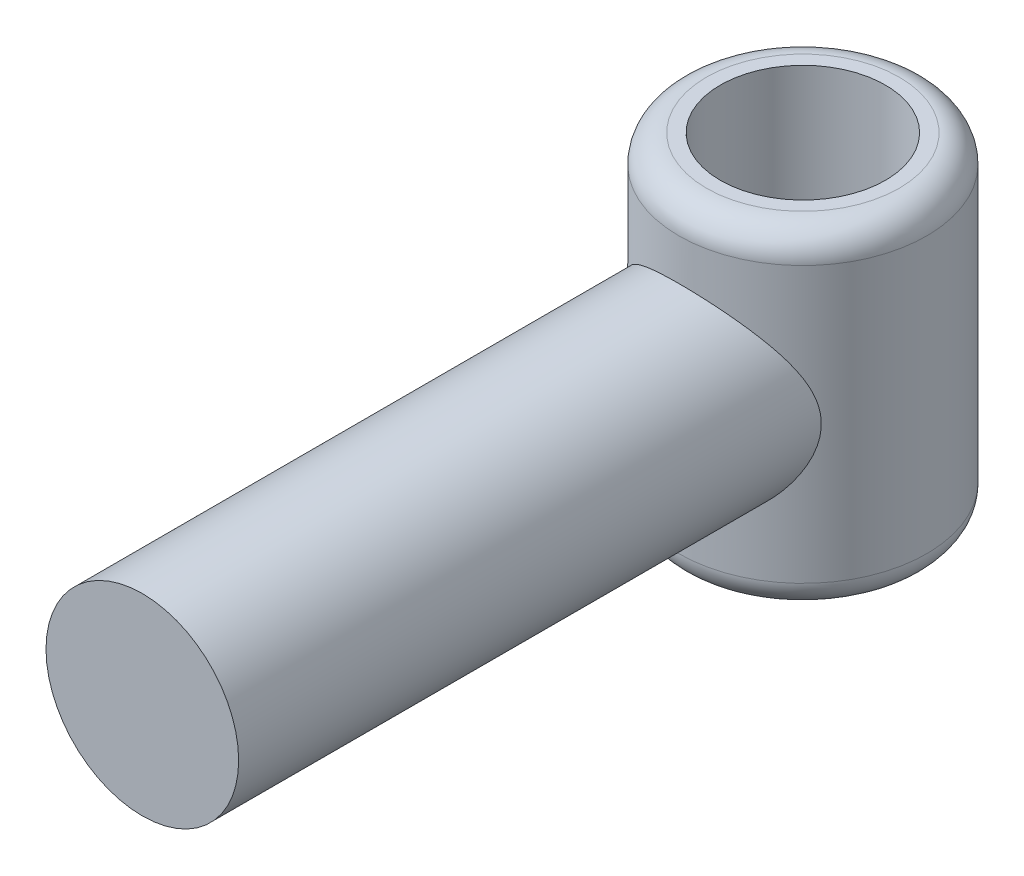
SolidWorks part; units mm, degrees
ref_plane "Front Plane" through (0, 0, 0) normal (0, 0, 1) x (1, 0, 0)
ref_plane "Top Plane" through (0, 0, 0) normal (0, 1, 0) x (1, 0, 0)
ref_plane "Right Plane" through (0, 0, 0) normal (1, 0, 0) x (0, 0, -1)
sketch "Sketch2" plane through (0, 0, 0) normal (0, 0, 1) x (1, 0, 0)
  circle A0 centre (0, 0) radius 22.225
  dimension "D1" = 44.45
extrude "Boss-Extrude1" add sketch "Sketch2" along normal blind 152.4
sketch "Sketch3" plane through (0, 0, 0) normal (0, 1, 0) x (1, 0, 0)
  circle A0 centre (0, 0) radius 28.575
  dimension "D1" = 57.15
extrude "Boss-Extrude2" add sketch "Sketch3" along normal blind 38.1 and the other way blind 38.1
sketch "Sketch4" plane through (0, 38.1, 0) normal (0, 1, 0) x (1, 0, 0)
  circle A0 centre (0, 0) radius 19.05
  dimension "D1" = 38.1
extrude "Cut-Extrude1" cut sketch "Sketch4" against normal blind 98.298
fillet "Fillet1" radius 6.35 2 edges at (0, -38.1, 28.575) (0, 38.1, 28.575)
